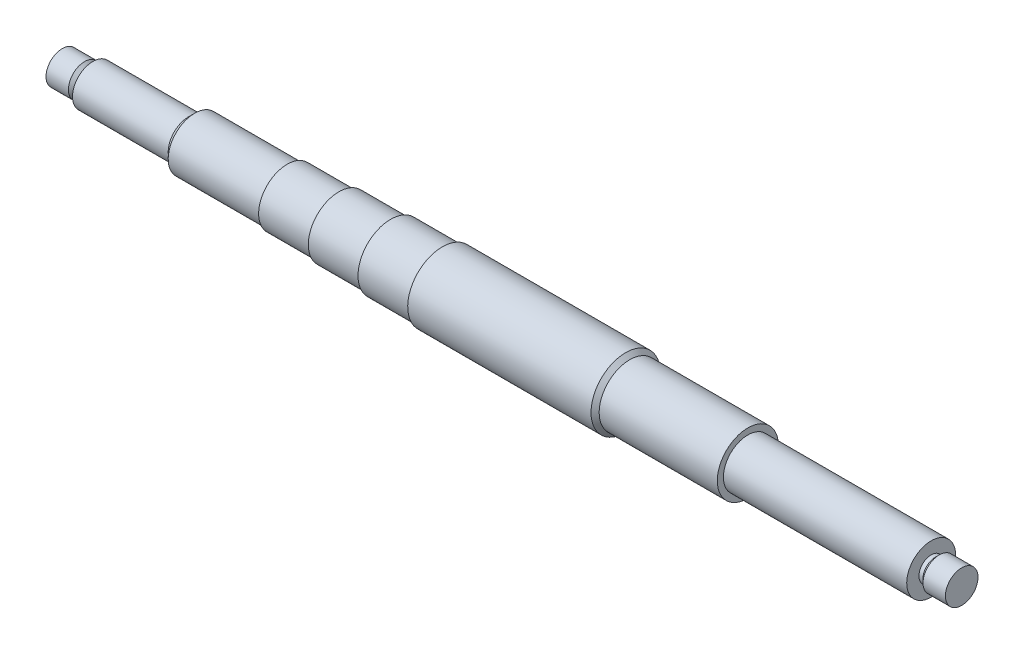
SolidWorks part; units mm, degrees
ref_plane "Front Plane" through (0, 0, 0) normal (0, 0, 1) x (1, 0, 0)
ref_plane "Top Plane" through (0, 0, 0) normal (0, 1, 0) x (1, 0, 0)
ref_plane "Right Plane" through (0, 0, 0) normal (1, 0, 0) x (0, 0, -1)
sketch "Sketch1" plane through (0, 0, 0) normal (0, 0, 1) x (1, 0, 0)
  line L0 (0, 0) -> (220.8, 0) construction
  line L4 (0, 0) -> (0, 4)
  line L5 (0, 4) -> (5.5, 4)
  line L6 (5.5, 4) -> (6.5, 3)
  line L7 (6.5, 3) -> (7.5, 3)
  line L11 (42.5, 6.5) -> (55.2, 6.5)
  line L12 (55.2, 6.5) -> (55.2, 7)
  line L13 (55.2, 7) -> (67.9, 7)
  line L14 (67.9, 7) -> (67.9, 7.5)
  line L15 (67.9, 7.5) -> (80.6, 7.5)
  line L16 (80.6, 7.5) -> (80.6, 8)
  line L17 (80.6, 8) -> (93.3, 8)
  line L18 (93.3, 8) -> (93.3, 8.5)
  line L19 (93.3, 8.5) -> (138.3, 8.5)
  line L21 (138.3, 8.5) -> (139.3, 7.5)
  line L22 (139.3, 7.5) -> (168.3, 7.5)
  line L23 (168.3, 7.5) -> (168.3, 6)
  line L24 (168.3, 6) -> (213.3, 6)
  line L25 (213.3, 6) -> (213.3, 3)
  line L26 (213.3, 3) -> (214.3, 3)
  line L27 (214.3, 3) -> (215.304, 4.004)
  line L28 (215.304, 4.004) -> (220.8, 4.004)
  line L31 (42.5, 6.5) -> (32.5, 6.5)
  line L32 (32.5, 6.5) -> (31, 5)
  line L33 (31, 5) -> (7.5, 5)
  line L34 (7.5, 5) -> (7.5, 3)
  line L35 (220.8, 4.004) -> (220.8, 0)
  line L36 (0, 0) -> (220.8, 0)
  point P1 (0, 0)
  dimension "D1" = 8.5
  dimension "D2" = 7.5
  dimension "D3" = 5
  dimension "D4" = 0.5
  dimension "D5" = 0.5
  dimension "D6" = 0.5
  dimension "D7" = 0.5
  dimension "D8" = 12.7
  dimension "D9" = 12.7
  dimension "D10" = 12.7
  dimension "D11" = 12.7
  dimension "D12" = 35
  dimension "D13" = 4
  dimension "D14" = 6.5
  dimension "D15" = 1
  dimension "D16" = 6
  dimension "D17" = 1
  dimension "D18" = 45
  dimension "D19" = 10
  dimension "D20" = 45
  dimension "D21" = 45
  dimension "D22" = 4.004
  dimension "D23" = 6.5
  dimension "D24" = 30
  dimension "D25" = 45
  dimension "D26" = 45
  dimension "D27" = 2
  dimension "D28" = 3
revolve "Revolve1" add sketch "Sketch1" angle 360 about L0
equation "\"Lab_Seal_Height\"= 0.089mm"
equation "\"Lab_Seal_Width\"= 12.7mm"
